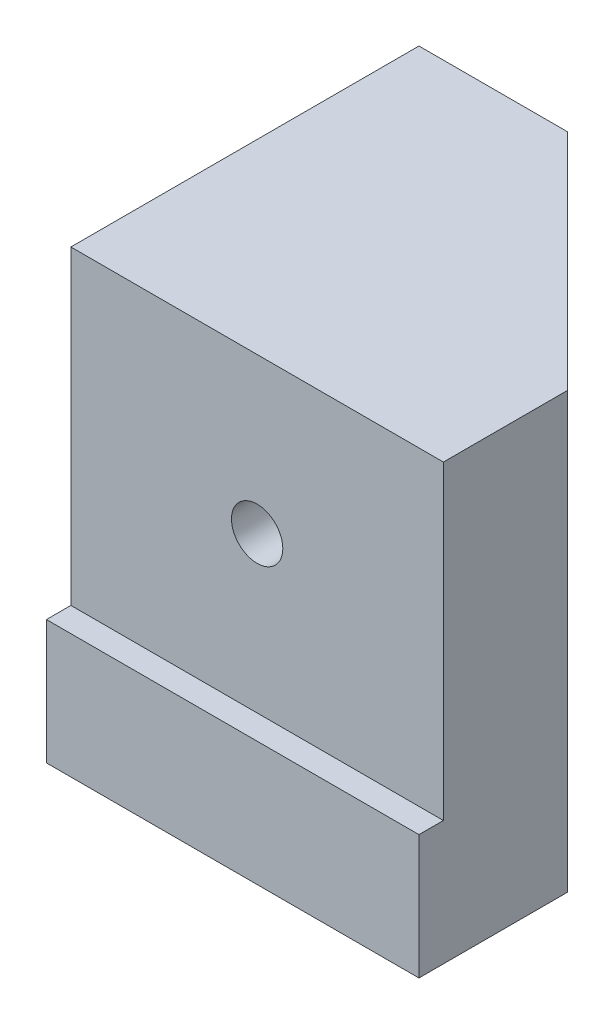
SolidWorks part; units mm, degrees
ref_plane "Front Plane" through (0, 0, 0) normal (0, 0, 1) x (1, 0, 0)
ref_plane "Top Plane" through (0, 0, 0) normal (0, 1, 0) x (1, 0, 0)
ref_plane "Right Plane" through (0, 0, 0) normal (1, 0, 0) x (0, 0, -1)
sketch "Sketch1" plane through (0, 0, 0) normal (0, 1, 0) x (1, 0, 0)
  line L1 (0, 0) -> (76.2, 0)
  line L2 (0, 0) -> (0, 76.2)
  line L3 (0, 76.2) -> (76.2, 76.2)
  line L4 (76.2, 0) -> (76.2, 76.2)
  dimension "D1" = 76.2
  dimension "D2" = 76.2
extrude "Boss-Extrude1" add sketch "Sketch1" along normal blind 88.9
sketch "Sketch2" plane through (0, 0, 0) normal (0, 0, 1) x (1, 0, 0)
  line L1 (0, 0) -> (38.1, 0)
  line L2 (0, 0) -> (0, 57.15)
  line L3 (0, 57.15) -> (38.1, 57.15)
  line L4 (38.1, 0) -> (38.1, 57.15)
  circle A0 centre (38.1, 57.15) radius 5.25
  dimension "D1" = 38.1
  dimension "D2" = 57.15
extrude "Cut-Extrude1" cut sketch "Sketch2" against normal blind 300 contours A0
sketch "Sketch3" plane through (0, 0, 0) normal (0, 0, 1) x (1, 0, 0)
  line L0 (76.2, 88.9) -> (76.2, 0) construction
  line L1 (0, 88.9) -> (76.2, 88.9)
  line L2 (0, 88.9) -> (0, 25.4)
  line L3 (0, 25.4) -> (76.2, 25.4)
  line L4 (76.2, 88.9) -> (76.2, 25.4)
  dimension "D1" = 63.5
extrude "Cut-Extrude2" cut sketch "Sketch3" against normal blind 5
sketch "Sketch4" plane through (0, 88.9, 0) normal (0, 1, 0) x (1, 0, 0)
  line L0 (76.2, 5) -> (76.2, 30.4)
  line L1 (76.2, 5) -> (76.2, 76.2) construction
  line L2 (76.2, 76.2) -> (0, 76.2) construction
  line L3 (76.2, 30.4) -> (30.4, 30.4)
  line L4 (76.2, 30.4) -> (76.2, 76.2)
  line L5 (76.2, 76.2) -> (30.4, 76.2)
  line L6 (30.4, 30.4) -> (30.4, 76.2)
  line L7 (76.2, 30.4) -> (30.4, 76.2)
  dimension "D1" = 25.4
  dimension "D2" = 45.8
  dimension "D3" = 45.8
extrude "Cut-Extrude4" cut sketch "Sketch4" against normal through all contours L7 L1 L2 region at (60.9333, 88.9, -60.9333)
